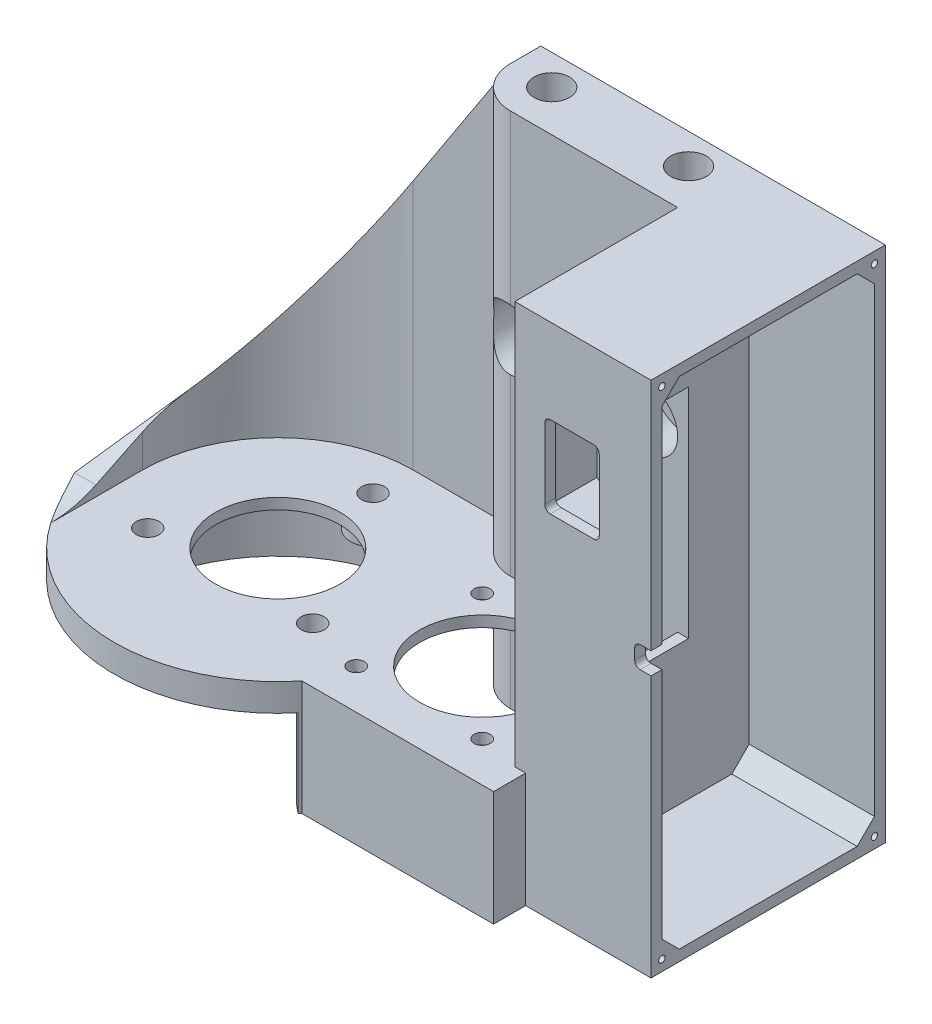
SolidWorks part; units mm, degrees
ref_plane "Front Plane" through (0, 0, 0) normal (0, 0, 1) x (1, 0, 0)
ref_plane "Top Plane" through (0, 0, 0) normal (0, 1, 0) x (1, 0, 0)
ref_plane "Right Plane" through (0, 0, 0) normal (1, 0, 0) x (0, 0, -1)
sketch "Sketch1" plane through (0, 0, 0) normal (0, 1, 0) x (1, 0, 0)
  line L0 (23.03, 10.795) -> (23.03, -10.795) construction
  line L2 (51.97, 0) -> (56.484, 0) construction
  line L3 (26.705, -14.47) -> (48.295, -14.47) construction
  line L5 (48.295, 14.47) -> (26.705, 14.47) construction
  line L6 (56.484, 30) -> (56.484, -13)
  line L10 (56.484, -18.8875) -> (23.308, -18.8875)
  line L11 (56.484, 8.5) -> (58.484, 8.5) construction
  line L12 (37.5, 0) -> (0, 0) construction
  line L19 (58.484, 28) -> (58.484, -11)
  line L20 (0, 0) -> (-21.95, 0) construction
  line L23 (56.484, 30) -> (81.484, 30)
  line L24 (58.484, 28) -> (81.484, 28)
  line L28 (58.484, -11) -> (58.484, -13) construction
  line L29 (81.484, 30) -> (81.484, 28)
  line L31 (68.984, 30) -> (68.984, -13) construction
  line L32 (0, 30) -> (56.484, 30)
  line L33 (58.484, -18.8875) -> (58.484, -13)
  line L34 (58.484, -13) -> (81.484, -13)
  line L35 (81.484, -13) -> (81.484, -11)
  line L36 (81.484, -11) -> (58.484, -11)
  line L40 (56.484, 16.8875) -> (25.8215, 16.8875) construction
  line L41 (58.484, -13) -> (56.484, -13)
  line L42 (51.97, -10.795) -> (51.97, 10.795) construction
  line L43 (81.484, 28) -> (81.484, -11) construction
  line L45 (18.2653, 24.4438) -> (56.484, 24.4438) construction
  line L46 (37.5, 0) -> (37.5, 14.47) construction
  line L47 (-21.95, 0) -> (-30, 0) construction
  line L48 (56.484, -18.8875) -> (56.484, -13) construction
  line L49 (58.484, -18.8875) -> (56.484, -18.8875)
  line L50 (37.5, 0) -> (51.97, 0) construction
  line L51 (18.2653, 24.4438) -> (18.2653, 30) construction
  line L52 (0, 0) -> (17.7923, 16.8429) construction
  line L53 (17.7923, 16.8429) -> (20.334, 19.2491) construction
  line L54 (20.334, 19.2491) -> (25.8215, 24.4438) construction
  line L55 (25.8215, 16.8875) -> (25.8215, 30) construction
  line L56 (37.5, -14.47) -> (37.5, -18.8875) construction
  line L57 (37.5, 14.47) -> (37.5, 16.8875) construction
  circle A0 centre (0, 0) radius 21.95 construction
  circle A1 centre (0, 0) radius 11.425
  arc A2 (23.03, 10.795) -> (26.705, 14.47) centre (26.705, 10.795) cw construction
  arc A3 (23.03, -10.795) -> (26.705, -14.47) centre (26.705, -10.795) ccw construction
  arc A4 (48.295, -14.47) -> (51.97, -10.795) centre (48.295, -10.795) ccw construction
  arc A5 (51.97, 10.795) -> (48.295, 14.47) centre (48.295, 10.795) ccw construction
  circle A9 centre (0, 0) radius 24.5 construction
  circle A10 centre (37.5, 0) radius 11.4982
  arc A18 (0, 30) -> (23.308, -18.8875) centre (0, 0) ccw
  arc A19 (25.8215, 16.8875) -> (18.2653, 24.4438) centre (25.8215, 24.4438) cw construction
  dimension "D2" = 22.85
  dimension "D5" = 3.675
  dimension "D7" = 22.9964
  dimension "D1" = 43.9
  dimension "D4" = 30
  dimension "D12" = 49
  dimension "D15" = 7.5563
  dimension "D3" = 2
  dimension "D9" = 25
  dimension "D10" = 43
  dimension "D6" = 14.47
  dimension "D8" = 37.5
  dimension "D13" = 38.2188
  dimension "D14" = 3.5
  dimension "D16" = 13.1125
  dimension "D11" = 4.4175
  dimension "D17" = 4.514
extrude "Boss-Extrude1" add sketch "Sketch1" against normal blind 2 contours A0 L3 A4 A5 L5 A10 A1 | L10 L3 A0 | L35 L36 L19 L34 region at (68.984, 0, -29.5026) region at (13.1889, 0, -3.0873)
extrude "Boss-Extrude2" add sketch "Sketch1<3>" along normal blind 73.934 and the other way blind 21.066 contours L6 L48 L41 L34 L35 L36 L19 L24 L29 L23 region at (68.984, 0, -29.5026)
sketch "Sketch1<3>" plane through (0, 0, 0) normal (0, 1, 0) x (1, 0, 0) same geometry as "Sketch1"
hole_wizard "M5x0.8 Tapped Hole1" positions "Sketch2" profile "Sketch3" tap size "M5x0.8" standard "ANSI Metric" end condition through all
sketch "Sketch2" plane through (0, 0, 0) normal (0, 1, 0) x (1, 0, 0)
  line L0 (-15.1338, -8.7375) -> (15.1338, 8.7375) construction
  line L2 (15.1338, -8.7375) -> (-15.1338, 8.7375) construction
  line L4 (0, 17.475) -> (0, -17.475) construction
  line L6 (0, 17.475) -> (-15.1338, -8.7375) construction
  line L7 (-15.1338, -8.7375) -> (15.1338, -8.7375) construction
  line L8 (15.1338, -8.7375) -> (0, 17.475) construction
  point P0 (0, 17.475)
  point P2 (-15.1338, -8.7375)
  point P4 (15.1338, -8.7375)
  dimension "D1" = 34.95
sketch "Sketch3" plane through (0, 0, -17.475) normal (1, 0, 0) x (0, 0, 1)
  line L0 (0, 0) -> (0, 21.066)
  line L1 (0, 21.066) -> (2.1, 21.066)
  line L2 (2.1, 21.066) -> (2.1, 0)
  line L5 (2.1, 0) -> (0, 0)
  line L11 (0, -6.35) -> (0, 107.95) construction
  dimension "Thru Tap Drill Dia." = 4.2
  dimension "Thru Tap Drill Depth" = 21.066
hole_wizard "#4 Clearance Hole1" positions "Sketch4" profile "Sketch5" hole size "#4" standard "ANSI Inch" end condition through all
sketch "Sketch4" plane through (0, 0, 0) normal (0, 1, 0) x (1, 0, 0)
  line L0 (25.943, 11.557) -> (49.057, 11.557) construction
  line L1 (49.057, 11.557) -> (49.057, -11.557) construction
  line L2 (49.057, -11.557) -> (25.943, -11.557) construction
  line L3 (25.943, -11.557) -> (25.943, 11.557) construction
  line L5 (37.5, 11.557) -> (37.5, -11.557) construction
  circle A5 centre (37.5, 0) radius 11.4982 construction
  point P0 (25.943, 11.557)
  point P2 (49.057, 11.557)
  point P4 (49.057, -11.557)
  point P6 (25.943, -11.557)
  point P35 (37.5, 0)
  dimension "D1" = 23.114
sketch "Sketch5" plane through (25.943, 0, -11.557) normal (1, 0, 0) x (0, 0, 1)
  line L0 (0, 0) -> (0, 21.066)
  line L1 (0, 21.066) -> (1.4732, 21.066)
  line L2 (1.4732, 21.066) -> (1.4732, 0)
  line L5 (1.4732, 0) -> (0, 0)
  line L11 (0, -6.35) -> (0, 107.95) construction
  dimension "Thru Hole Dia." = 2.9464
  dimension "Thru Hole Depth" = 21.066
sketch "Sketch8" plane through (0, 73.934, 0) normal (0, 1, 0) x (1, 0, 0)
  line L0 (56.484, 30) -> (56.484, -13) construction
  line L1 (56.484, 30) -> (81.484, 30)
  line L2 (56.484, 30) -> (56.484, -13)
  line L3 (56.484, -13) -> (81.484, -13)
  line L4 (81.484, 30) -> (81.484, -13)
  line L6 (56.484, -13) -> (81.484, -13) construction
extrude "Boss-Extrude4" add sketch "Sketch8" against normal blind 2
sketch "Sketch9" plane through (0, -21.066, 0) normal (0, -1, 0) x (1, 0, 0)
  line L1 (56.484, 13) -> (81.484, 13)
  line L2 (56.484, 13) -> (56.484, -30)
  line L3 (56.484, -30) -> (81.484, -30)
  line L4 (81.484, 13) -> (81.484, -30)
  line L8 (56.484, 13) -> (81.484, 13) construction
extrude "Boss-Extrude5" add sketch "Sketch9" against normal blind 2
sketch "Sketch65" plane through (58.484, 0, 0) normal (1, 0, 0) x (0, 0, -1)
  line L0 (-11, 71.934) -> (-7.825, 71.934)
  line L1 (-11, 71.934) -> (28, 71.934) construction
  line L2 (-7.825, 71.934) -> (-11, 68.759)
  line L3 (-11, -19.066) -> (-11, 71.934) construction
  line L4 (-11, 68.759) -> (-11, 71.934)
  line L5 (28, 71.934) -> (24.825, 71.934)
  line L6 (-11, 71.934) -> (28, 71.934) construction
  line L7 (24.825, 71.934) -> (28, 68.759)
  line L8 (28, -19.066) -> (28, 71.934) construction
  line L9 (28, 68.759) -> (28, 71.934)
  line L10 (28, -15.891) -> (24.825, -19.066)
  line L11 (28, -19.066) -> (-11, -19.066) construction
  line L12 (24.825, -19.066) -> (28, -19.066)
  line L13 (28, -19.066) -> (28, -15.891)
  line L14 (-7.825, -19.066) -> (-11, -15.891)
  line L15 (28, -19.066) -> (-11, -19.066) construction
  line L16 (-11, -15.891) -> (-11, -19.066)
  line L17 (-11, -19.066) -> (-7.825, -19.066)
  dimension "D1" = 3.175
extrude "Boss-Extrude34" add sketch "Sketch65" along normal up to surface (23 mm away) up to face at (81.484, 26.434, -8.5)
sketch "Sketch28" plane through (56.484, 0, 0) normal (-1, 0, 0) x (0, 0, 1)
  line L1 (-18.8875, 67.584) -> (-30, 67.584)
  line L3 (-16.8875, 73.934) -> (-30, 73.934)
  line L4 (-30, 67.584) -> (-30, 73.934)
  line L5 (-30, 0) -> (13, 0) construction
  line L6 (-18.8875, 0) -> (-18.8875, 67.584)
  line L7 (-18.8875, 0) -> (-16.8875, 0)
  line L9 (-16.8875, 0) -> (-16.8875, 73.934)
  dimension "D1" = 11.1125
  dimension "D2" = 6.35
  dimension "D3" = 2
extrude "Boss-Extrude17" add sketch "Sketch28" along normal blind 38.2188
sketch "Sketch44" plane through (18.2653, 0, 0) normal (-1, 0, 0) x (0, 0, 1)
  line L0 (-18.8875, 67.584) -> (-18.8875, 0) construction
  line L1 (-18.8875, 67.584) -> (-30, 67.584)
  line L2 (-18.8875, 67.584) -> (-18.8875, 0)
  line L3 (-18.8875, 0) -> (-30, 0)
  line L4 (-30, 67.584) -> (-30, 0)
  line L5 (-30, 67.584) -> (-18.8875, 67.584) construction
extrude "Boss-Extrude21" add sketch "Sketch44" against normal blind 2
sketch "Sketch46" plane through (0, 0, 0) normal (0, 1, 0) x (1, 0, 0)
  line L0 (20.2653, 30) -> (56.484, 30) construction
  line L1 (56.484, 30) -> (20.2653, 30)
  line L5 (20.2653, 30) -> (20.2653, 18.8875)
  line L6 (20.2653, 18.8875) -> (56.484, 18.8875)
  line L8 (20.2653, 18.8875) -> (56.484, 18.8875) construction
  line L9 (56.484, 18.8875) -> (56.484, 30)
extrude "Cut-Extrude12" cut sketch "Sketch46" against normal through all
sketch "Sketch47" plane through (0, -21.066, 0) normal (0, -1, 0) x (1, 0, 0)
  line L1 (18.2653, -16.8875) -> (56.484, -16.8875)
  line L2 (18.2653, -16.8875) -> (18.2653, -30)
  line L3 (18.2653, -30) -> (56.484, -30)
  line L4 (56.484, -16.8875) -> (56.484, -30)
extrude "Boss-Extrude23" add sketch "Sketch47" against normal blind 6.35
sketch "Sketch45" plane through (0, -14.716, 0) normal (0, 1, 0) x (1, 0, 0)
  line L0 (25.8215, 18.8875) -> (20.2653, 18.8875)
  line L2 (20.2653, 18.8875) -> (20.2653, 24.4437)
  line L5 (56.484, 18.8875) -> (50.9278, 18.8875)
  line L9 (56.484, 18.8875) -> (56.484, 24.4437)
  line L10 (56.484, 30) -> (56.484, 16.8875) construction
  line L11 (20.2653, 18.8875) -> (56.484, 18.8875) construction
  line L14 (56.484, 30) -> (56.484, 18.8875) construction
  line L15 (20.2653, 30) -> (20.2653, 18.8875) construction
  arc A0 (20.2653, 24.4437) -> (25.8215, 18.8875) centre (25.8215, 24.4437) ccw
  arc A1 (56.484, 24.4437) -> (50.9278, 18.8875) centre (50.9278, 24.4437) cw
extrude "Boss-Extrude22" add sketch "Sketch45" along normal up to surface (88.65 mm away) up to face at (52.0778, 73.934, -11.2958)
hole_wizard "1/4 Clearance Hole3" positions "Sketch30" profile "Sketch31" hole size "1/4" standard "ANSI Inch" end condition through all
sketch "Sketch30" plane through (0, 73.934, 0) normal (0, 1, 0) x (1, 0, 0)
  arc A2 (50.9278, 18.8875) -> (56.484, 24.4437) centre (50.9278, 24.4437) ccw construction
  arc A3 (20.2653, 24.4437) -> (25.8215, 18.8875) centre (25.8215, 24.4437) ccw construction
  point P0 (50.9278, 24.4437)
  point P2 (25.8215, 24.4437)
sketch "Sketch31" plane through (50.9278, 73.934, -24.4437) normal (1, 0, 0) x (0, 0, 1)
  line L0 (0, 0) -> (0, 95)
  line L1 (0, 95) -> (3.2639, 95)
  line L2 (3.2639, 95) -> (3.2639, 0)
  line L5 (3.2639, 0) -> (0, 0)
  line L11 (0, -6.35) -> (0, 107.95) construction
  dimension "Thru Hole Dia." = 6.5278
  dimension "Thru Hole Depth" = 95
sketch "Sketch32" plane through (0, 73.934, 0) normal (0, 1, 0) x (1, 0, 0)
  line L0 (25.8215, 16.8875) -> (18.2653, 16.8875)
  line L2 (18.2653, 16.8875) -> (18.2653, 24.4437)
  line L5 (22.5576, 24.4437) -> (18.2653, 24.4437) construction
  line L6 (25.8215, 24.4437) -> (22.5576, 24.4437) construction
  arc A0 (18.2653, 24.4437) -> (25.8215, 16.8875) centre (25.8215, 24.4437) ccw
  circle A2 centre (25.8215, 24.4437) radius 3.2639 construction
extrude "Cut-Extrude5" cut sketch "Sketch32" against normal up to surface (73.934 mm away) up to face at (25.943, 0, -10.0838)
sketch "Sketch48" plane through (0, -21.066, 0) normal (0, -1, 0) x (1, 0, 0)
  line L0 (56.484, -18.8875) -> (56.484, -16.8875)
  line L2 (56.484, -16.8875) -> (18.2653, -16.8875)
  line L3 (18.2653, -16.8875) -> (18.2653, -30)
  line L4 (0, -30) -> (20.2653, -30) construction
  line L5 (18.2653, -30) -> (20.2653, -30)
  line L6 (20.2653, -30) -> (20.2653, -18.8875)
  line L7 (20.2653, -18.8875) -> (56.484, -18.8875)
  dimension "D1" = 2
extrude "Boss-Extrude24" add sketch "Sketch48" against normal up to surface (19.066 mm away) up to face at (25.943, -2, -10.0838)
sketch "Sketch49" plane through (0, -21.066, 0) normal (0, -1, 0) x (1, 0, 0)
  line L0 (18.2653, -24.4437) -> (18.2653, -16.8875)
  line L2 (18.2653, -16.8875) -> (25.8215, -16.8875)
  arc A0 (18.2653, -24.4437) -> (25.8215, -16.8875) centre (25.8215, -24.4437) cw
  circle A1 centre (25.8215, -24.4437) radius 3.2639 construction
extrude "Cut-Extrude13" cut sketch "Sketch49" against normal up to surface (19.066 mm away) up to face at (25.943, -2, -10.0838)
sketch "Sketch12" plane through (0, 0, -30) normal (0, 0, -1) x (-1, 0, 0)
  line L0 (-18.2653, 73.934) -> (30, 0)
  line L1 (30, 0) -> (-18.2653, 0)
  line L3 (-18.2653, 0) -> (-18.2653, 73.934)
  line L4 (0, 0) -> (-18.2653, 0) construction
  line L5 (30, 0) -> (-23.308, 0) construction
extrude "Boss-Extrude6" add sketch "Sketch12" against normal blind 5.1625
ref_plane "Plane5" through (26.29, 0, 0) normal (-1, 0, 0) x (0, 0, 1)
sketch "Sketch14" plane through (0, 0, 0) normal (0, -1, 0) x (1, 0, 0)
  line L0 (-30, -24.8375) -> (-30, -30) construction
  line L2 (-30, 0) -> (-30, -30)
  line L3 (-30, -30) -> (0, -30)
  line L4 (0, 30) -> (-30, 30)
  line L9 (-30, 30) -> (-30, 0)
  arc A0 (-30, 0) -> (0, -30) centre (0, 0) ccw
  arc A2 (23.308, 18.8875) -> (0, -30) centre (0, 0) ccw construction
  arc A7 (0, 30) -> (-30, 0) centre (0, 0) ccw
extrude "Cut-Extrude4" cut sketch "Sketch14" against normal through all contours L2 L3 A0 | L9 A7 L4
sketch "Sketch17" plane through (0, 0, 0) normal (0, 1, 0) x (1, 0, 0)
  line L3 (0, 24.8375) -> (-16.8255, 24.8375)
  line L6 (18.2653, 24.8375) -> (-16.8255, 24.8375) construction
  line L8 (-24.8375, 0) -> (-24.8375, -16.8255)
  arc A0 (0, 24.8375) -> (-24.8375, 0) centre (0, 0) ccw
  arc A1 (-16.8255, 24.8375) -> (23.308, -18.8875) centre (0, 0) ccw construction
  arc A3 (-16.8255, 24.8375) -> (-24.8375, -16.8255) centre (0, 0) ccw
extrude "Boss-Extrude7" add sketch "Sketch17" along normal up to surface (45.9548 mm away) up to face at (4.8295, 53.3527, -27.7342)
sketch "Sketch37" plane through (-24.8375, 0, 0) normal (1, 0, 0) x (0, 0, -1)
  line L0 (-16.8255, 7.9081) -> (-16.8255, 0) construction
  line L1 (-8.543, 1.9027) -> (7.4976, 9.6829)
  line L3 (-16.8255, 0) -> (-16.8255, 9.6829)
  line L4 (-16.8255, 0) -> (0, 0) construction
  line L5 (-16.8255, 9.6829) -> (7.4976, 9.6829)
  arc A0 (-16.8255, 0) -> (-8.543, 1.9027) centre (-16.8255, 18.9788) ccw
  ellipse E0 centre (0, 45.9548) end of major axis (0, 91.9096) minor radius 30 (-16.8255, 7.9081) -> (-22.2801, 15.1808) ccw construction
  ellipse E1 centre (0, 45.9548) end of major axis (0, 7.9081) minor radius 24.8375 (0, 7.9081) -> (24.8375, 45.9548) ccw construction
extrude "Cut-Extrude8" cut sketch "Sketch37" against normal through all and the other way up to surface other way up to face at (-14.9908, 11.4958, -14.9908)
hole_wizard "1/4 Clearance Hole2" positions "Sketch24" profile "Sketch25" hole size "1/4" standard "ANSI Inch" end condition through all
sketch "Sketch24" plane through (0, 0, -16.8875) normal (0, 0, -1) x (-1, 0, 0)
  line L1 (-50.9278, 37.5603) -> (-50.9278, 62.9602) construction
  line L4 (-50.9278, 37.5603) -> (-50.9278, 0) construction
  line L11 (-50.9278, 62.9602) -> (-50.9278, 73.934) construction
  line L13 (-54.1917, 73.934) -> (-47.6639, 73.934) construction
  line L14 (-50.9278, 37.5603) -> (-25.5278, 37.5603) construction
  line L16 (-25.8215, 0) -> (-56.484, 0) construction
  point P2 (-50.9278, 37.5603)
  point P51 (-25.5278, 37.5603)
  dimension "D1" = 25.4
  dimension "D2" = 37.5603
sketch "Sketch25" plane through (50.9278, 37.5603, -16.8875) normal (1, 0, 0) x (0, -1, 0)
  line L0 (0, 0) -> (0, 13.1125)
  line L1 (0, 13.1125) -> (3.2639, 13.1125)
  line L2 (3.2639, 13.1125) -> (3.2639, 0)
  line L5 (3.2639, 0) -> (0, 0)
  line L11 (0, -6.35) -> (0, 107.95) construction
  dimension "Thru Hole Dia." = 6.5278
  dimension "Thru Hole Depth" = 13.1125
sketch "Sketch57" plane through (0, 0, -30) normal (0, 0, -1) x (-1, 0, 0)
  line L0 (-25.5278, 44.529) -> (-32.7903, 44.529)
  line L1 (-50.9278, 62.9602) -> (-50.9278, 37.5603) construction
  line L2 (-32.7903, 44.529) -> (-32.7903, 30.5915)
  line L4 (-20.2653, 44.529) -> (-20.2653, 30.5915)
  line L5 (-56.484, 69.2227) -> (-43.959, 69.2227) construction
  line L6 (-56.484, -14.716) -> (-56.484, 67.584) construction
  line L7 (-43.959, 69.2227) -> (-43.959, 56.6978) construction
  line L8 (-43.959, 56.6978) -> (-56.484, 56.6978) construction
  line L9 (-56.484, 56.6978) -> (-56.484, 69.2227) construction
  line L10 (-50.9278, 62.9602) -> (-43.959, 62.9602) construction
  line L11 (-25.5278, 44.529) -> (-25.5278, 37.5603) construction
  line L12 (-25.5278, 37.5603) -> (-25.5278, 30.5915) construction
  line L13 (-56.484, 44.529) -> (-56.484, 30.5915)
  line L14 (-56.484, 30.5915) -> (-43.959, 30.5915)
  line L15 (-43.959, 30.5915) -> (-43.959, 44.529)
  line L16 (-43.959, 44.529) -> (-56.484, 44.529)
  line L17 (-43.959, 30.5915) -> (-32.7903, 30.5915) construction
  line L18 (-32.7903, 44.529) -> (-43.959, 44.529) construction
  line L19 (-43.959, 56.6978) -> (-43.959, 44.529) construction
  line L20 (-20.2653, 37.5603) -> (-32.7903, 37.5603) construction
  line L21 (-20.2653, 30.5915) -> (-32.7903, 30.5915)
  line L22 (-20.2653, 44.529) -> (-25.5278, 44.529)
  line L23 (-20.2653, 67.584) -> (-20.2653, -14.716) construction
  circle A0 centre (-50.9278, 37.5603) radius 3.2639
  circle A1 centre (-50.9278, 62.9602) radius 3.2639 construction
  arc A3 (-50.9278, 34.2964) -> (-50.9278, 40.8241) centre (-50.9278, 37.5603) ccw construction
  circle A4 centre (-25.5278, 37.5603) radius 3.2639
  arc A5 (-25.8215, 40.8109) -> (-25.8215, 34.3096) centre (-25.5278, 37.5603) ccw construction
  point P38 (-32.7903, 44.529)
  dimension "D1" = 25.4
  dimension "D2" = 7.2625
extrude "Boss-Extrude29" add sketch "Sketch57" against normal up to surface (11.1125 mm away) up to face at (38.3379, 31.9971, -18.8875)
sketch "Sketch26" plane through (0, -2, 0) normal (0, -1, 0) x (1, 0, 0)
  line L0 (18.2653, -30) -> (0, -30)
  line L1 (58.484, 18.8875) -> (23.308, 18.8875) construction
  line L3 (56.484, 18.8875) -> (58.484, 18.8875)
  line L5 (58.484, 18.8875) -> (58.484, 13)
  line L7 (18.2653, -28) -> (18.2653, -30)
  line L8 (0, -30) -> (18.2653, -30) construction
  line L9 (0, -28) -> (18.2653, -28)
  line L14 (81.484, 13) -> (56.484, 13) construction
  line L15 (18.2653, -24.4437) -> (18.2653, -30) construction
  line L16 (22.3341, 16.8875) -> (56.484, 16.8875)
  line L17 (56.484, -16.8875) -> (56.484, 13) construction
  line L19 (56.484, 18.8875) -> (23.308, 18.8875)
  line L20 (58.484, 13) -> (56.484, 13)
  line L21 (56.484, 13) -> (56.484, 16.8875)
  line L23 (56.484, 16.8875) -> (56.484, 18.8875) construction
  arc A2 (22.3341, 16.8875) -> (0, -28) centre (0, 0) ccw
  arc A3 (0, -30) -> (23.308, 18.8875) centre (0, 0) cw
  arc A8 (23.308, 18.8875) -> (0, -30) centre (0, 0) ccw construction
  dimension "D1" = 2
extrude "Boss-Extrude15" add sketch "Sketch26" along normal up to surface (19.066 mm away) up to face at (50.9278, -21.066, -21.1799)
sketch "Sketch41" plane through (56.484, 0, 0) normal (-1, 0, 0) x (0, 0, 1)
  line L0 (-16.8875, 46.434) -> (-28, 46.434) construction
  line L1 (-16.8875, 6.434) -> (-0.1125, 6.434)
  line L2 (-16.8875, 6.434) -> (-16.8875, 46.434)
  line L3 (-16.8875, 46.434) -> (-0.1125, 46.434)
  line L4 (-0.1125, 6.434) -> (-0.1125, 46.434)
  line L5 (-28, -15.891) -> (-28, 68.759) construction
  line L6 (-0.1125, 46.434) -> (11, 46.434) construction
  line L7 (11, -15.891) -> (11, 68.759) construction
  line L8 (-8.5, 46.434) -> (-8.5, 71.934) construction
  line L10 (7.825, 71.934) -> (-24.825, 71.934) construction
  line L11 (-8.5, 6.434) -> (-8.5, -19.066) construction
  line L12 (-24.825, -19.066) -> (7.825, -19.066) construction
  line L13 (-16.8875, 0) -> (-16.8875, 73.934) construction
  dimension "D1" = 40
extrude "Cut-Extrude10" cut sketch "Sketch41" against normal through all
sketch "Sketch58" plane through (0, 73.934, 0) normal (0, 1, 0) x (1, 0, 0)
  line L0 (18.2653, 24.4437) -> (18.2653, 16.8875)
  line L1 (18.2653, 16.8875) -> (25.8215, 16.8875)
  arc A0 (18.2653, 24.4437) -> (25.8215, 16.8875) centre (25.8215, 24.4437) ccw
  arc A1 (18.2653, 24.4437) -> (25.8215, 16.8875) centre (25.8215, 24.4437) ccw construction
extrude "Cut-Extrude14" cut sketch "Sketch58" against normal up to surface (73.934 mm away) up to face at (25.943, 0, -10.0838)
sketch "Sketch60" plane through (0, 0, -16.8875) normal (0, 0, 1) x (1, 0, 0)
  circle A0 centre (25.5278, 37.5603) radius 4.7625
  arc A2 (25.8215, 34.3096) -> (25.8215, 40.8109) centre (25.5278, 37.5603) ccw construction
  circle A3 centre (25.5278, 37.5603) radius 3.2639
  dimension "D1" = 9.525
extrude "Boss-Extrude31" add sketch "Sketch60" against normal up to surface up to face at (22.1882, 37.1568, -19.0329)
sketch "Sketch66" plane through (0, 0, -16.8875) normal (0, 0, 1) x (1, 0, 0)
  line L0 (25.5278, 37.5603) -> (50.9278, 37.5603) construction
  line L1 (50.9278, 37.5603) -> (50.9278, 62.9602) construction
  circle A0 centre (50.9278, 62.9602) radius 5.5562 construction
  circle A1 centre (50.9278, 37.5603) radius 5.5562
  circle A2 centre (25.5278, 37.5603) radius 5.5563
  circle A5 centre (50.9278, 37.5603) radius 3.2639 construction
  circle A6 centre (25.5278, 37.5603) radius 3.2639 construction
  dimension "D1" = 11.1125
extrude "Cut-Extrude16" cut sketch "Sketch66" against normal offset from surface (6.7625 mm away) 6.35 up to face at (36.2467, 30.3382, -30)
sketch "Sketch67" plane through (81.484, 0, 0) normal (1, 0, 0) x (0, 0, -1)
  line L0 (30, 72.934) -> (-13, 72.934) construction
  line L1 (30, -21.066) -> (30, 73.934) construction
  line L2 (-13, -21.066) -> (-13, 73.934) construction
  line L3 (8.5, 71.934) -> (8.5, 73.934) construction
  line L4 (-7.825, 71.934) -> (24.825, 71.934) construction
  line L5 (30, 73.934) -> (-13, 73.934) construction
  line L6 (8.5, -19.066) -> (8.5, -21.066) construction
  line L7 (24.825, -19.066) -> (-7.825, -19.066) construction
  line L8 (-13, -21.066) -> (30, -21.066) construction
  line L9 (-13, -20.066) -> (30, -20.066) construction
  line L10 (8.5, 72.934) -> (8.5, 41.934) construction
  line L12 (8.5, 41.934) -> (8.5, 10.934) construction
  line L13 (8.5, 10.934) -> (8.5, -20.066) construction
  line L14 (-13, 41.934) -> (30, 41.934) construction
  line L15 (30, 10.934) -> (-13, 10.934) construction
  point P12 (8.5, 72.934)
  point P21 (8.5, -20.066)
ref_plane "Plane7" through (0, 41.934, 0) normal (0, 1, 0) x (1, 0, 0)
ref_plane "Plane8" through (0, 10.934, 0) normal (0, 1, 0) x (1, 0, 0)
sketch "Sketch70" plane through (81.484, 0, 0) normal (1, 0, 0) x (0, 0, -1)
  line L0 (8.5, 71.934) -> (8.5, -19.066) construction
  line L1 (-11, 71.934) -> (28, 71.934) construction
  line L2 (-11, 71.934) -> (-11, -19.066) construction
  line L3 (-11, -19.066) -> (28, -19.066) construction
  line L4 (28, 71.934) -> (28, -19.066) construction
  line L5 (-11, 26.434) -> (28, 26.434) construction
  line L6 (-11, -15.891) -> (-11, 68.759) construction
  line L7 (28, -15.891) -> (28, 68.759) construction
  circle A0 centre (-11, 71.934) radius 0.595
  circle A1 centre (28, 71.934) radius 0.595
  circle A2 centre (28, -19.066) radius 0.595
  circle A3 centre (-11, -19.066) radius 0.595
  point P16 (8.5, 26.434)
  dimension "D1" = 1.19
  dimension "D2" = 39
  dimension "D3" = 91
extrude "Cut-Extrude17" cut sketch "Sketch70" against normal blind 10
sketch "Sketch71" plane through (0, 0, 13) normal (0, 0, 1) x (1, 0, 0)
  line L0 (81.484, 30.934) -> (79.484, 30.934)
  line L1 (62.984, 58.434) -> (70.984, 58.434)
  line L2 (61.984, 57.434) -> (61.984, 44.434)
  line L3 (62.984, 43.434) -> (70.984, 43.434)
  line L4 (71.984, 57.434) -> (71.984, 44.434)
  line L5 (81.484, -21.066) -> (81.484, 73.934) construction
  line L6 (78.484, 29.934) -> (78.484, 27.934)
  line L7 (79.484, 26.934) -> (81.484, 26.934)
  line L8 (81.484, 26.934) -> (81.484, 30.934)
  line L9 (78.484, 28.934) -> (81.484, 28.934) construction
  line L10 (78.484, 28.934) -> (78.484, -21.066) construction
  line L11 (81.484, -21.066) -> (58.484, -21.066) construction
  line L12 (71.984, 58.434) -> (61.984, 43.434) construction
  line L13 (81.484, 50.934) -> (66.984, 50.934) construction
  line L14 (66.984, 50.934) -> (66.984, -21.066) construction
  line L15 (81.484, -21.066) -> (58.484, -21.066) construction
  arc A0 (79.484, 30.934) -> (78.484, 29.934) centre (79.484, 29.934) ccw
  arc A1 (78.484, 27.934) -> (79.484, 26.934) centre (79.484, 27.934) ccw
  arc A2 (62.984, 58.434) -> (61.984, 57.434) centre (62.984, 57.434) ccw
  arc A3 (70.984, 58.434) -> (71.984, 57.434) centre (70.984, 57.434) cw
  arc A4 (70.984, 43.434) -> (71.984, 44.434) centre (70.984, 44.434) ccw
  arc A5 (61.984, 44.434) -> (62.984, 43.434) centre (62.984, 44.434) ccw
  point P29 (61.984, 58.434)
  point P35 (71.984, 43.434)
  dimension "D2" = 1
  dimension "D9" = 1
  dimension "D1" = 4
  dimension "D3" = 3
  dimension "D4" = 50
  dimension "D5" = 15
  dimension "D6" = 10
  dimension "D7" = 72
  dimension "D8" = 14.5
extrude "Cut-Extrude19" cut sketch "Sketch71" against normal up to surface (2 mm away) up to face at (69.984, 26.434, 11)
sketch "Sketch54" [suppressed] plane through (25.6142, 0, 0) normal (-1, 0, 0) x (0, 0, 1)
  line L0 (-16.25, 32.004) -> (18.25, 0)
  line L1 (18.25, 0) -> (-16.25, 0)
  line L2 (-16.25, 0) -> (-16.25, 32.004)
  line L3 (-16.25, 32.004) -> (-16.25, 42.529) construction
  line L4 (-16.25, 32.004) -> (-16.25, 37.2665) construction
  line L5 (-16.25, 34.0026) -> (-16.25, 40.5304) construction
  dimension "D1" = 5.2625
extrude "Boss-Extrude27" [suppressed] add sketch "Sketch54" along normal mid plane 2
sketch "Sketch55" [suppressed] plane through (0, 0, -16.25) normal (0, 0, -1) x (-1, 0, 0)
  line L1 (-26.6142, 32.004) -> (-24.6142, 32.004)
  line L2 (-26.6142, 32.004) -> (-26.6142, 0)
  line L3 (-26.6142, 0) -> (-24.6142, 0)
  line L4 (-24.6142, 32.004) -> (-24.6142, 0)
extrude "Boss-Extrude28" [suppressed] add sketch "Sketch55" along normal up to surface (0.0195 mm away) up to face at (21.8072, 37.2088, -19.3456)
sketch "Sketch61" [suppressed] plane through (24.6142, 0, 0) normal (-1, 0, 0) x (0, 0, 1)
  line L0 (-16.2695, 32.004) -> (-16.2695, 32.0221)
  line L1 (-16.2695, 32.004) -> (-16.25, 32.004) construction
  line L2 (-16.2695, 32.0221) -> (-16.25, 32.004)
  line L3 (-16.25, 32.004) -> (-16.2695, 32.004) construction
  line L4 (18.25, 0) -> (-16.25, 32.004) construction
  line L5 (-16.25, 32.004) -> (-16.2695, 32.004)
extrude "Boss-Extrude32" [suppressed] add sketch "Sketch61" along normal up to surface (0.5315 mm away) up to face at (21.8072, 37.2088, -19.3456)
ref_plane "Plane6" [suppressed] through (0, 54.07, 0) normal (0, 1, 0) x (1, 0, 0)
sketch "Sketch62" [suppressed] plane through (0, 54.07, 0) normal (0, -1, 0) x (1, 0, 0)
  line L0 (55.8082, 14.225) -> (5.3474, -23.775)
  line L1 (5.3474, -23.775) -> (17.8832, -23.775)
  line L5 (17.8832, -23.775) -> (17.8832, -23.5125)
  line L6 (25.1457, -16.25) -> (55.8082, -16.25)
  line L7 (55.8082, -16.25) -> (55.8082, 14.225)
  arc A0 (17.8832, -23.5125) -> (25.1457, -16.25) centre (25.1457, -23.5125) cw
extrude "Boss-Extrude33" [suppressed] add sketch "Sketch62" against normal blind 2
sketch "Sketch63" [suppressed] plane through (0, 0, -23.775) normal (0, 0, -1) x (-1, 0, 0)
  line L1 (0, 45.5966) -> (-17.8832, 73.934) construction
  line L6 (-5.3474, 54.07) -> (-5.3474, 56.07)
  line L7 (-5.3474, 56.07) -> (-6.6096, 56.07)
  line L8 (-6.6096, 56.07) -> (-5.3474, 54.07)
extrude "Cut-Extrude15" [suppressed] cut sketch "Sketch63" against normal through all
sketch "Sketch59" [suppressed] plane through (0, 0, -28.775) normal (0, 0, -1) x (-1, 0, 0)
  line L0 (-19.8832, 67.584) -> (-55.8082, 67.584) construction
  line L1 (-38.8457, 67.584) -> (-36.8457, 67.584)
  line L2 (-38.8457, 67.584) -> (-38.8457, 27.434)
  line L3 (-38.8457, -14.716) -> (-36.8457, -14.716)
  line L4 (-36.8457, 67.584) -> (-36.8457, 27.434)
  line L5 (-19.8832, -14.716) -> (-55.8082, -14.716) construction
  line L6 (-37.8457, 67.584) -> (-37.8457, -14.716) construction
  line L7 (-55.8082, 27.434) -> (-38.8457, 27.434)
  line L9 (-55.8082, 25.434) -> (-38.8457, 25.434)
  line L12 (-55.8082, -14.716) -> (-55.8082, 30.004) construction
  line L15 (-36.8457, 27.434) -> (-19.8832, 27.434)
  line L17 (-38.8457, 25.434) -> (-38.8457, -14.716)
  line L20 (-36.8457, 25.434) -> (-36.8457, -14.716)
  line L23 (-36.8457, 25.434) -> (-19.8832, 25.434)
  line L25 (-19.8832, 30.004) -> (-19.8832, -14.716) construction
  line L26 (-55.8082, 27.434) -> (-55.8082, 25.434)
  line L27 (-19.8832, 27.434) -> (-19.8832, 25.434)
  line L29 (-55.8082, 26.434) -> (-19.8832, 26.434) construction
  point P8 (-37.8457, 67.584)
  point P17 (-37.8457, -14.716)
  dimension "D1" = 2
extrude "Boss-Extrude30" [suppressed] add sketch "Sketch59" against normal up to surface (10.525 mm away) up to face at (38.3746, 33.8515, -18.8875)
sketch "Sketch68" plane through (0, 41.934, 0) normal (0, 1, 0) x (1, 0, 0)
  line L0 (81.484, 28) -> (58.484, 28)
  line L1 (58.484, 28) -> (58.484, 16.8875)
  line L2 (58.484, 16.8875) -> (81.484, 28)
  line L4 (81.484, -11) -> (58.484, -11)
  line L5 (58.484, -11) -> (58.484, 0.1125)
  line L6 (58.484, 0.1125) -> (81.484, -11)
extrude "Boss-Extrude35" [suppressed] add sketch "Sketch68" along normal mid plane 2
sketch "Sketch69" plane through (0, 10.934, 0) normal (0, 1, 0) x (1, 0, 0)
  line L0 (81.484, 28) -> (58.484, 28)
  line L1 (58.484, 28) -> (58.484, 16.8875)
  line L2 (58.484, 16.8875) -> (81.484, 28)
  line L3 (58.484, -11) -> (58.484, 0.1125)
  line L4 (58.484, 0.1125) -> (81.484, -11)
  line L5 (81.484, -11) -> (58.484, -11)
extrude "Boss-Extrude36" [suppressed] add sketch "Sketch69" along normal mid plane 2
sketch "Sketch72" plane through (0, 0, 0) normal (-1, 0, 0) x (0, 0, 1)
  line L1 (30, -5.04) -> (28, -5.04)
  line L2 (30, -5.04) -> (30, -21.066)
  line L3 (30, -21.066) -> (28, -21.066)
  line L4 (28, -5.04) -> (28, -21.066)
  line L7 (28, -5.04) -> (28, -2) construction
  line L8 (-11.425, -2) -> (11.425, -2) construction
  line L9 (30, -21.066) -> (30, 0) construction
  dimension "D1" = 2
  dimension "D3" = 3.04
revolve "Cut-Revolve1" cut sketch "Sketch72" angle 50 about axis through (0, -127.9745, 0) along (0, 1, 0) other way angle 70
sketch "Sketch73" plane through (0, -2, 0) normal (0, -1, 0) x (1, 0, 0)
  circle A0 centre (-15.1338, 8.7375) radius 2.1
  circle A1 centre (15.1338, 8.7375) radius 2.1
  circle A2 centre (0, -17.475) radius 2.1
  circle A3 centre (0, -17.475) radius 2.1 construction
  circle A4 centre (15.1338, 8.7375) radius 2.1 construction
  circle A5 centre (-15.1338, 8.7375) radius 2.1 construction
  circle A6 centre (-15.1338, 8.7375) radius 4.1
  circle A7 centre (15.1338, 8.7375) radius 4.1
  circle A8 centre (0, -17.475) radius 4.1
  dimension "D1" = 2
extrude "Boss-Extrude37" add sketch "Sketch73" along normal offset from surface (3.66 mm away) 5.66 up to face at (23.5176, 0, -1.7051)
ref_plane "Plane9" through (0, 39.434, 0) normal (0, -1, 0) x (-1, 0, 0)
sketch "Sketch75" plane through (0, 39.434, 0) normal (0, -1, 0) x (-1, 0, 0)
  line L0 (-81.484, -11) -> (-58.484, -11)
  line L1 (-81.484, -11) -> (-58.484, 0.1125)
  line L2 (-58.484, 0.1125) -> (-58.484, -11)
extrude "Boss-Extrude38" add sketch "Sketch75" along normal mid plane 2
equation "\"mc\"= 0.5'minimum clearance"
equation "\"D2@Sketch1\"=\"chd\"+2*\"mc\""
equation "\"chd\"= 21.85000000'commutator hub diameter"
equation "\"cfd\"= 43.90000000'commutator flange diameter"
equation "\"D1@Boss-Extrude1\"=\"mint\""
equation "\"mint\"= 2'minimum thickness"
equation "\"D7@Sketch1\"=.86600000in+2*\"mc\""
equation "\"D1@Sketch1\"=\"cfd\""
equation "\"D3@Sketch1\"=\"mint\""
